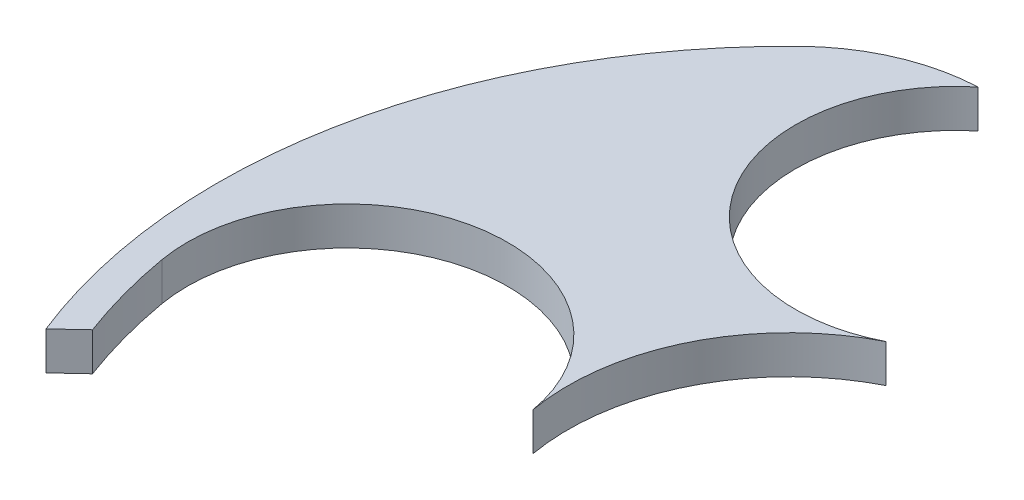
SolidWorks part; units mm, degrees
ref_plane "Plan de face" through (0, 0, 0) normal (0, 0, 1) x (1, 0, 0)
ref_plane "Plan de dessus" through (0, 0, 0) normal (0, 1, 0) x (1, 0, 0)
ref_plane "Plan de droite" through (0, 0, 0) normal (1, 0, 0) x (0, 0, -1)
sketch "Esquisse1" plane through (0, 0, 0) normal (0, 1, 0) x (1, 0, 0)
  line L0 (-85.9873, -39.219) -> (-82.8372, -36.2731)
  line L3 (-9.4508, 5.6286) -> (-14.9085, -3.5351) construction
  line L5 (3.3105, -15.9387) -> (9.4508, -5.6286) construction
  line L12 (0, 0) -> (-80, 0) construction
  line L13 (-64.4502, -24.994) -> (-51.2217, 24.3754) construction
  line L14 (-65, 0) -> (-64.4502, -24.994) construction
  arc A0 (-44.8834, -16.4709) -> (3.3105, -15.9387) centre (-21.2415, 25) ccw construction
  arc A1 (-20.1052, -3.4627) -> (-14.9085, -3.5351) centre (-17.486, -2) ccw construction
  arc A2 (-20.1052, -3.4627) -> (-29.494, 14.405) centre (325.5264, 189.5538) cw construction
  arc A3 (-15.0496, 17.5397) -> (-22.3476, -39.7999) centre (-16.3245, -11.4322) ccw
  arc A4 (-86.2446, -23.7683) -> (-82.8372, -36.2731) centre (-16.3245, -11.4322) ccw
  arc A36 (-51.2217, 24.3754) -> (-64.4502, -24.994) centre (-16.3245, -11.4322) ccw construction
  arc A37 (-68.6703, 42.2792) -> (-85.9873, -39.219) centre (-16.3245, -11.4322) ccw
  arc A41 (9.4508, -5.6286) -> (-9.4508, 5.6286) centre (0, 0) ccw construction
  arc A42 (-16.402, 38.5677) -> (-47.4539, -50.5598) centre (-16.3245, -11.4322) ccw construction
  arc A43 (-52.3505, 49.3499) -> (-29.494, 14.405) centre (-39.0306, 33.1147) ccw
  arc A44 (-52.3505, 49.3499) -> (-68.6703, 42.2792) centre (-51.2217, 24.3754) ccw
  arc A45 (-44.8834, -16.4709) -> (-86.2446, -23.7683) centre (-65.564, -20.1196) ccw
  point P78 (-56.6847, 2.6915)
  point P85 (-65, 0)
  dimension "D4" = 25
  dimension "D5" = 12
  dimension "D6" = 21
  dimension "D8" = 25
  dimension "D10" = 3
  dimension "D11" = 17.6
  dimension "D18" = 80
  dimension "D20" = 75
  dimension "D26" = 11
  dimension "D13" = 50
  dimension "D14" = 21
  dimension "D12" = 2
  dimension "D22" = 25
  dimension "D23" = 75
  dimension "D24" = 28
  dimension "D25" = 15
  dimension "D30" = 15
  dimension "D32" = 5
extrude "Boss.-Extru.1" add sketch "Esquisse1" along normal blind 5 contours A45 A3 A43 A44 A37 L0 region at (-68.2362, 0, -11.4594)
